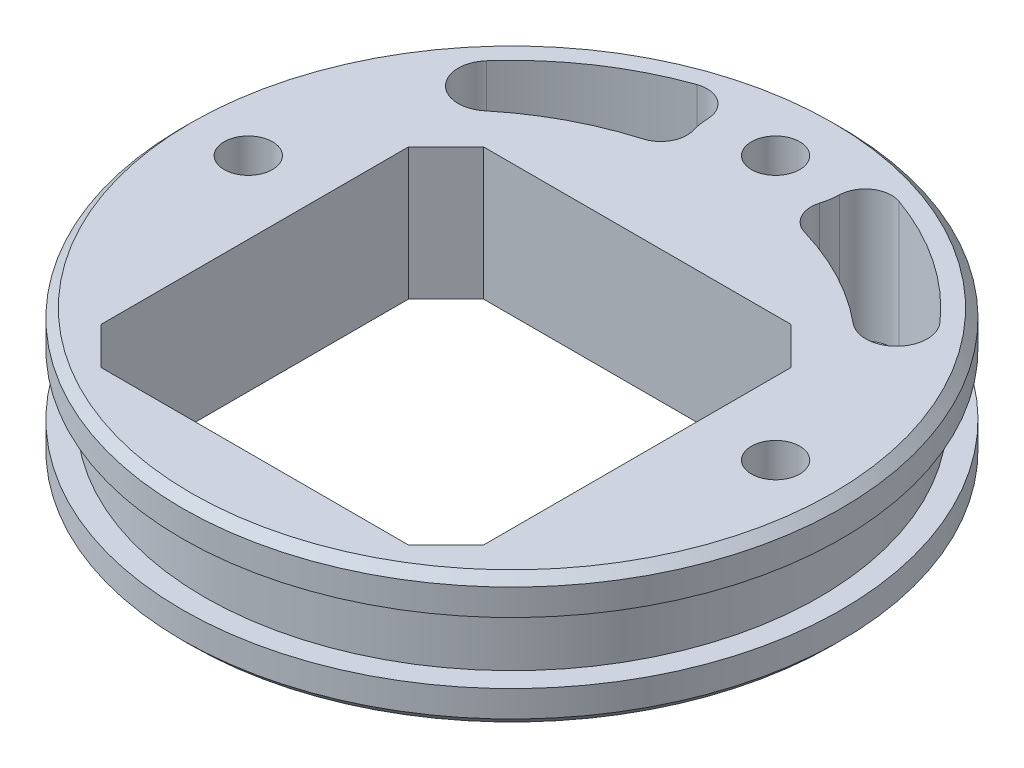
SolidWorks part; units mm, degrees
ref_plane "Front Plane" through (0, 0, 0) normal (0, 0, 1) x (1, 0, 0)
ref_plane "Top Plane" through (0, 0, 0) normal (0, 1, 0) x (1, 0, 0)
ref_plane "Right Plane" through (0, 0, 0) normal (1, 0, 0) x (0, 0, -1)
sketch "Sketch1" plane through (0, 0, 0) normal (0, 1, 0) x (1, 0, 0)
  line L0 (0, 0) -> (0, -7.5) construction
  line L1 (-17.4944, 14.25) -> (17.4944, 14.25)
  line L2 (17.4944, 14.25) -> (21.75, 9.9944)
  line L3 (21.75, 9.9944) -> (21.75, -24.9944)
  line L4 (21.75, -24.9944) -> (17.4944, -29.25)
  line L5 (17.4944, -29.25) -> (-17.4944, -29.25)
  line L6 (-17.4944, -29.25) -> (-21.75, -24.9944)
  line L7 (-21.75, -24.9944) -> (-21.75, 9.9944)
  line L8 (-21.75, 9.9944) -> (-17.4944, 14.25)
  circle A0 centre (0, 0) radius 35 construction
  circle A1 centre (0, -7.5) radius 27.9127 construction
  circle A2 centre (0, 0) radius 30 construction
  circle A3 centre (0, 30) radius 2.75
  circle A4 centre (30, 0) radius 2.75
  circle A5 centre (-30, 0) radius 2.75
  circle A6 centre (0, 0) radius 37.5
  arc A7 (-20.9585, 17.8769) -> (20.9585, 17.8769) centre (0, -7.5) ccw construction
  arc A8 (7.1823, 27.8402) -> (7.4969, 29.7857) centre (0, 30) ccw
  arc A9 (6.4062, 33.9) -> (-6.4062, 33.9) centre (0, 0) ccw construction
  arc A10 (-25.8051, 22.8986) -> (-20.9585, 17.8769) centre (-23.1872, 20.5755) ccw
  arc A11 (20.9585, 17.8769) -> (25.8051, 22.8986) centre (23.1872, 20.5755) ccw
  arc A12 (-5.5389, 24.9433) -> (5.5389, 24.9433) centre (0, 30) ccw construction
  arc A13 (5.5389, 24.9433) -> (-5.5389, 24.9433) centre (0, -7.5) ccw construction
  arc A14 (-9.2152, 24.0963) -> (-20.9585, 17.8769) centre (0, -7.5) ccw
  arc A15 (20.9585, 17.8769) -> (9.2152, 24.0963) centre (0, -7.5) ccw
  arc A16 (25.8051, 22.8986) -> (11.4953, 32.5286) centre (0, 0) ccw
  arc A17 (-11.4953, 32.5286) -> (-25.8051, 22.8986) centre (0, 0) ccw
  arc A18 (-25.8051, 22.8986) -> (25.8051, 22.8986) centre (0, 0) ccw construction
  arc A19 (-7.4969, 29.7857) -> (-7.1823, 27.8402) centre (0, 30) ccw
  arc A20 (6.4062, 33.9) -> (-6.4062, 33.9) centre (0, 30) ccw construction
  arc A21 (11.4953, 32.5286) -> (7.4969, 29.7857) centre (10.4957, 29.7) ccw
  arc A22 (7.1823, 27.8402) -> (9.2152, 24.0963) centre (10.0552, 26.9763) ccw
  arc A23 (-9.2152, 24.0963) -> (-7.1823, 27.8402) centre (-10.0552, 26.9763) ccw
  arc A24 (-11.4953, 32.5286) -> (-7.4969, 29.7857) centre (-10.4957, 29.7) cw
  point P23 (5.0719, 35.525)
  point P33 (-6.4062, 34.0027)
  point P34 (6.294, 34.0786)
  dimension "D1" = 43.5
  dimension "D2" = 70
  dimension "D5" = 60
  dimension "D6" = 5.5
  dimension "D7" = 2.5
  dimension "D8" = 3
  dimension "D9" = 5
  dimension "D10" = 3.5
  dimension "D11" = 3
  dimension "D3" = 7.5
  dimension "D4" = 55.5
extrude "Boss-Extrude1" add sketch "Sketch1" along normal mid plane 15
sketch "Sketch2" plane through (0, 0, 0) normal (0, 1, 0) x (1, 0, 0)
  circle A0 centre (0, 0) radius 35
  dimension "D1" = 70
extrude "Cut-Extrude-Thin1" cut sketch "Sketch2" against normal mid plane 7 thin thin type one direction wall 10
chamfer "Chamfer1" distance 1 angle 45 2 edges at (0, -7.5, 37.5) (0, 7.5, 37.5)
